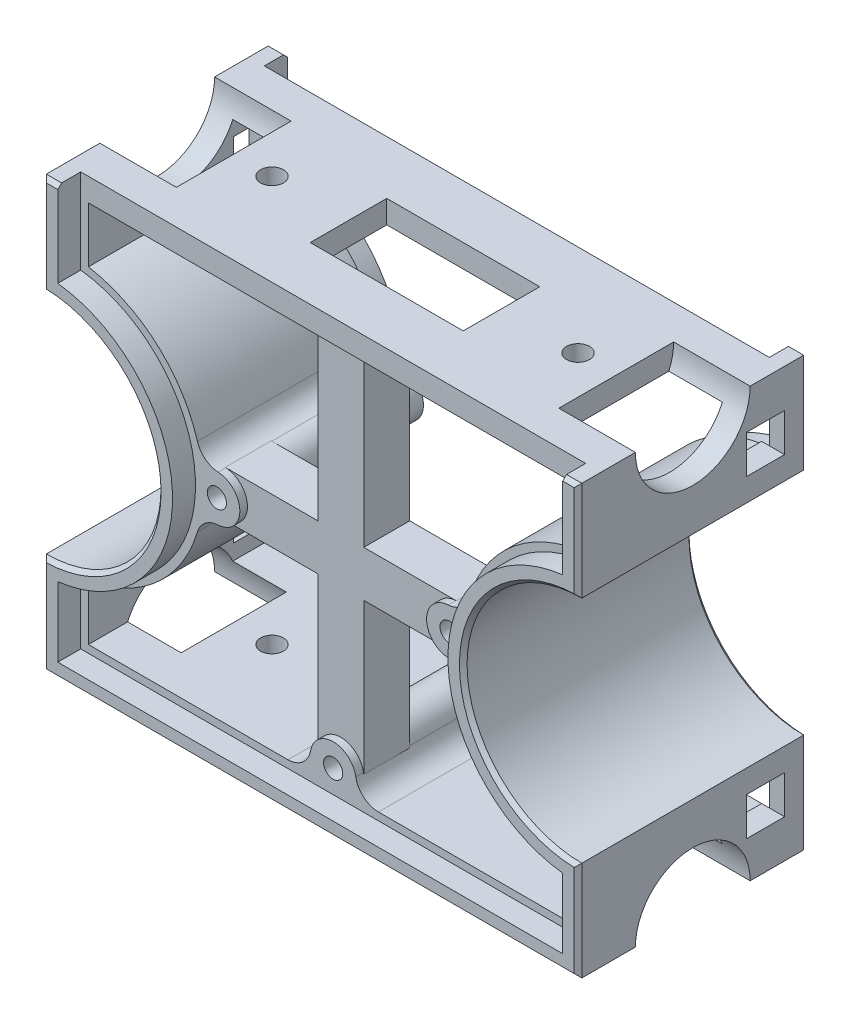
SolidWorks part; units mm, degrees
ref_plane "Front Plane" through (0, 0, 0) normal (0, 0, 1) x (1, 0, 0)
ref_plane "Top Plane" through (0, 0, 0) normal (0, 1, 0) x (1, 0, 0)
ref_plane "Right Plane" through (0, 0, 0) normal (1, 0, 0) x (0, 0, -1)
sketch "Sketch1" plane through (0, 0, 0) normal (0, 1, 0) x (1, 0, 0)
  line L1 (-35, -15) -> (35, -15)
  line L2 (-35, -15) -> (-35, 15)
  line L3 (-35, 15) -> (35, 15)
  line L4 (35, -15) -> (35, 15)
  line L5 (-35, -15) -> (35, 15) construction
  line L6 (-35, 15) -> (35, -15) construction
  point P0 (0, 0)
  dimension "D1" = 30
  dimension "D2" = 70
extrude "Boss-Extrude1" add sketch "Sketch1" along normal blind 56
sketch "Sketch2" plane through (0, 0, -15) normal (0, 0, -1) x (-1, 0, 0)
  line L0 (35, 56) -> (35, 0) construction
  line L1 (32, 53) -> (-32, 53)
  line L2 (32, 53) -> (32, 45.7482)
  line L3 (32, 3) -> (-32, 3)
  line L4 (-32, 53) -> (-32, 45.7482)
  line L5 (32, 53) -> (-32, 3) construction
  line L6 (32, 3) -> (-32, 53) construction
  line L7 (-35, 56) -> (-35, 0) construction
  line L8 (-35, 0) -> (35, 0) construction
  line L9 (-35, 56) -> (35, 56) construction
  line L10 (-32, 10.2518) -> (-32, 3)
  line L11 (32, 10.2518) -> (32, 3)
  line L12 (-33, 54) -> (-33, 44.8819)
  line L13 (33, 54) -> (33, 44.8819)
  line L14 (33, 2) -> (-33, 2)
  line L15 (-33, 11.1181) -> (-33, 2)
  line L16 (33, 11.1181) -> (33, 2)
  line L17 (33, 54) -> (-33, 54)
  arc A0 (-32, 10.2518) -> (-32, 45.7482) centre (-35, 28) ccw
  arc A1 (32, 45.7482) -> (32, 10.2518) centre (35, 28) ccw
  arc A2 (-33, 11.1181) -> (-33, 44.8819) centre (-35, 28) ccw
  arc A3 (33, 44.8819) -> (33, 11.1181) centre (35, 28) ccw
  point P0 (0, 28)
  dimension "D5" = 36
  dimension "D6" = 36
  dimension "D9" = 0
  dimension "D10" = 17
  dimension "D13" = 0
  dimension "D14" = 17
  dimension "D1" = 3
  dimension "D2" = 3
  dimension "D3" = 3
  dimension "D4" = 3
  dimension "D7" = 1
  dimension "D8" = 1
  dimension "D11" = 1
  dimension "D12" = 1
extrude "Cut-Extrude1" cut sketch "Sketch2" against normal through all contours A1 L11 L3 L10 A0 L4 L1 L2
sketch "Sketch3" plane through (0, 0, 0) normal (0, -1, 0) x (1, 0, 0)
  circle A0 centre (20, 0) radius 1.5
  circle A1 centre (-20, 0) radius 1.5
  dimension "D1" = 3
  dimension "D2" = 3
  dimension "D3" = 20
  dimension "D4" = 20
extrude "Cut-Extrude2" cut sketch "Sketch3" against normal blind 5 and the other way through all
sketch "Sketch4" plane through (35, 0, 0) normal (1, 0, 0) x (0, 0, -1)
  line L0 (-15, 56) -> (15, 56) construction
  line L1 (-15, 0) -> (15, 0) construction
  circle A0 centre (0, 56) radius 7.5
  circle A1 centre (0, 0) radius 7.5
  dimension "D1" = 15
  dimension "D2" = 15
extrude "Cut-Extrude5" cut sketch "Sketch4" against normal blind 10
sketch "Sketch6" plane through (0, 0, 15) normal (0, 0, 1) x (1, 0, 0)
  line L0 (-35, 56) -> (-35, 0) construction
  line L1 (35, 56) -> (35, 0) construction
  circle A0 centre (-35, 28) radius 15
  circle A1 centre (35, 28) radius 15
  dimension "D1" = 30
extrude "Cut-Extrude7" cut sketch "Sketch6" against normal through all
sketch "Sketch7" plane through (0, 56, 0) normal (0, 1, 0) x (1, 0, 0)
  line L1 (-10, 5) -> (10, 5)
  line L2 (-10, 5) -> (-10, -5)
  line L3 (-10, -5) -> (10, -5)
  line L4 (10, 5) -> (10, -5)
  line L5 (-10, 5) -> (10, -5) construction
  line L6 (-10, -5) -> (10, 5) construction
  point P0 (0, 0)
  dimension "D1" = 20
  dimension "D2" = 10
extrude "Cut-Extrude8" cut sketch "Sketch7" against normal blind 10
sketch "Sketch8" plane through (0, 56, 0) normal (0, 1, 0) x (1, 0, 0)
  circle A0 centre (20, 0) radius 1.5
  circle A1 centre (-20, 0) radius 1.5
  dimension "D1" = 3
  dimension "D2" = 3
  dimension "D3" = 40
  dimension "D4" = 20
extrude "Cut-Extrude10" cut sketch "Sketch8" against normal blind 10
extrude "Cut-Extrude11" cut sketch "Sketch2<3>" against normal blind 3
sketch "Sketch2<3>" plane through (0, 0, -15) normal (0, 0, -1) x (-1, 0, 0) same geometry as "Sketch2"
sketch "Sketch11" plane through (0, 0, 15) normal (0, 0, 1) x (1, 0, 0)
  line L0 (17, 28) -> (-17, 28) construction
  line L1 (0, 53) -> (0, 3) construction
  line L2 (-32, 3) -> (32, 3) construction
  line L3 (-3, 3) -> (3, 3)
  line L4 (3, 3) -> (3, 25)
  line L5 (3, 25) -> (17.2518, 25)
  line L6 (-3, 3) -> (-3, 25)
  line L7 (-3, 25) -> (-17.2518, 25)
  line L8 (-3, 31) -> (-17.2518, 31)
  line L9 (-3, 53) -> (-3, 31)
  line L10 (-3, 53) -> (3, 53)
  line L11 (3, 53) -> (3, 31)
  line L12 (3, 31) -> (17.2518, 31)
  arc A0 (32, 45.7482) -> (32, 10.2518) centre (35, 28) ccw construction
  arc A2 (17.2518, 31) -> (17.2518, 25) centre (35, 28) ccw
  arc A3 (-17.2518, 31) -> (-17.2518, 25) centre (-35, 28) cw
  point P13 (0, 28)
  dimension "D1" = 3
  dimension "D2" = 3
extrude "Boss-Extrude2" add sketch "Sketch11" against normal blind 6 from offset 4 offset against normal yes
chamfer "Chamfer1" distance 0.5 angle 45 16 edges at (0, 56, 15) (35, 49.5, 15) (20, 28, 15) (35, 6.5, 15) (0, 0, 15) (-35, 6.5, 15) (-20, 28, 15) (-35, 49.5, 15) (-17, 28, 15) (-32, 6.6259, 15) (0, 3, 15) (32, 6.6259, 15) (17, 28, 15) (32, 49.3741, 15) (0, 53, 15) (-32, 49.3741, 15)
chamfer "Chamfer2" distance 0.5 angle 45 8 edges at (-35, 6.5, -15) (-20, 28, -15) (-35, 49.5, -15) (0, 56, -15) (35, 49.5, -15) (20, 28, -15) (0, 0, -15) (35, 6.5, -15)
sketch "Sketch10" plane through (0, 0, -15) normal (0, 0, -1) x (-1, 0, 0)
  line L0 (-35, 56) -> (35, 56) construction
  line L1 (33, 54) -> (-33, 54)
  line L2 (33, 54) -> (33, 56)
  line L3 (33, 56) -> (-33, 56)
  line L4 (-33, 54) -> (-33, 56)
  line L5 (-33, 54) -> (-33, 44.8819) construction
extrude "Cut-Extrude13" cut sketch "Sketch10" against normal blind 3
mirror "Mirror2" about plane through (0, 0, 0) normal (0, 0, 1) of "Cut-Extrude13", "Cut-Extrude11"
sketch "Sketch12" plane through (35, 0, 0) normal (1, 0, 0) x (0, 0, -1)
  line L0 (15, 12.5081) -> (15, 0.5) construction
  line L1 (7, 10) -> (12, 10)
  line L2 (7, 10) -> (7, 5)
  line L3 (7, 5) -> (12, 5)
  line L4 (12, 10) -> (12, 5)
  line L5 (7.5, 0) -> (14.5, 0) construction
  line L6 (-15, 28) -> (15, 28) construction
  line L7 (-15, 43.4919) -> (-15, 12.5081) construction
  line L8 (15, 12.5081) -> (15, 43.4919) construction
  line L9 (12, 46) -> (12, 51)
  line L10 (7, 51) -> (12, 51)
  line L11 (7, 46) -> (7, 51)
  line L12 (7, 46) -> (12, 46)
  dimension "D1" = 5
  dimension "D2" = 3
  dimension "D3" = 5
  dimension "D4" = 5
extrude "Cut-Extrude14" cut sketch "Sketch12" against normal up to surface (3 mm away) up to face at (32, 6.1673, 0)
mirror "Mirror3" about plane through (0, 0, 0) normal (1, 0, 0) of "Cut-Extrude14"
mirror "Mirror4" about plane through (0, 0, 0) normal (1, 0, 0) of "Cut-Extrude5"
sketch "Sketch13" plane through (0, 0, -12) normal (0, 0, -1) x (-1, 0, 0)
  line L0 (-17, 28) -> (17, 28) construction
  line L1 (0, 53) -> (0, 3) construction
  line L2 (32, 53) -> (-32, 53) construction
  line L3 (-32, 3) -> (32, 3) construction
  line L4 (3, 3) -> (-3, 3) construction
  line L5 (-2.2361, 3) -> (2.2361, 3)
  arc A0 (-17.2518, 25) -> (-17.2518, 31) centre (-35, 28) ccw construction
  arc A1 (32, 45.7482) -> (32, 10.2518) centre (35, 28) ccw construction
  arc A2 (-17.1459, 30.2873) -> (-17.1459, 25.7127) centre (-15.2047, 28) cw
  arc A3 (-32, 10.2518) -> (-32, 45.7482) centre (-35, 28) ccw construction
  arc A4 (-17.1459, 30.2873) -> (-17.1459, 25.7127) centre (-35.2047, 28) cw
  arc A5 (17.1459, 30.2873) -> (17.1459, 25.7127) centre (35.2047, 28) ccw
  arc A6 (17.1459, 30.2873) -> (17.1459, 25.7127) centre (15.2047, 28) ccw
  arc A7 (-2.2361, 3) -> (2.2361, 3) centre (0, 5) cw
  dimension "D1" = 3
  dimension "D3" = 3
  dimension "D2" = 20
  dimension "D4" = 2
extrude "Boss-Extrude3" add sketch "Sketch13" against normal up to surface (24 mm away)
hole_wizard "Tap Drill for M3x0.5 Tap1" positions "Sketch14" profile "Sketch15" hole size "M3x0.5" standard "ANSI Metric" end condition through all
sketch "Sketch14" plane through (0, 0, -12) normal (0, 0, -1) x (-1, 0, 0)
  point P0 (-15.2047, 28)
  point P3 (15.2047, 28)
  point P7 (0, 5)
sketch "Sketch15" plane through (15.2047, 28, -12) normal (1, 0, 0) x (0, 1, 0)
  line L0 (0, 0) -> (0, 27)
  line L1 (0, 27) -> (1.25, 27)
  line L2 (1.25, 27) -> (1.25, 0)
  line L5 (1.25, 0) -> (0, 0)
  line L11 (0, -6.35) -> (0, 107.95) construction
  dimension "Thru Hole Dia." = 2.5
  dimension "Thru Hole Depth" = 27
fillet "Fillet1" radius 3 6 edges at (-2.2361, 3, -3.5) (2.2361, 3, -3.5)
